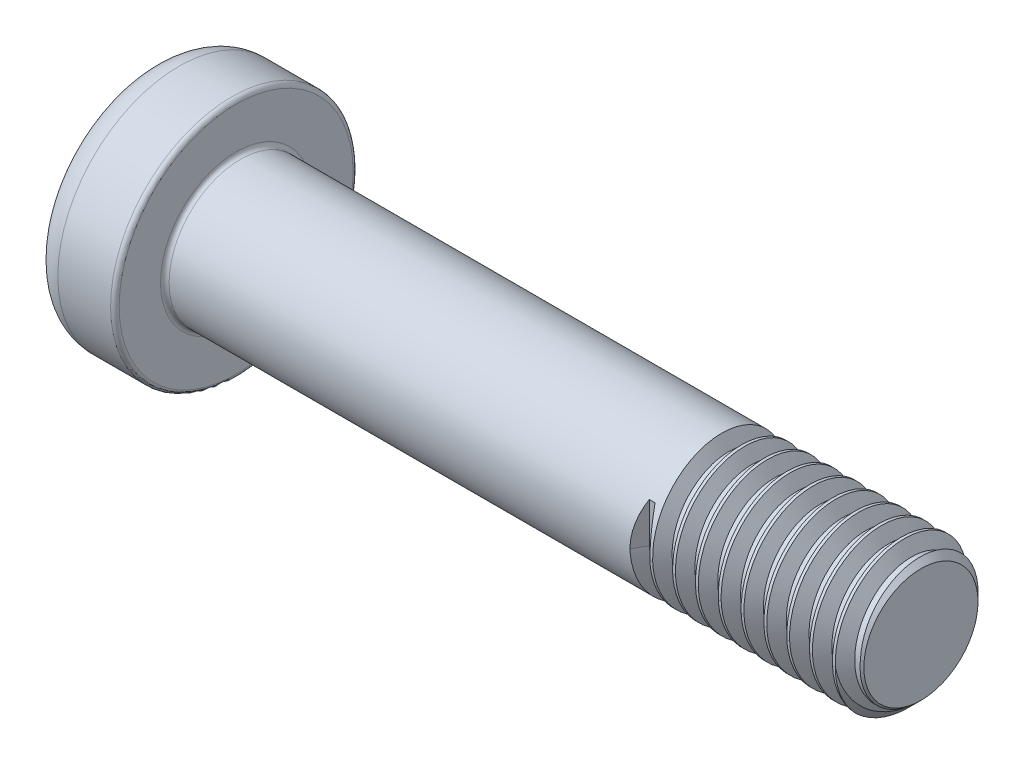
SolidWorks part; units mm, degrees
material "Acier inoxydable chromé"
ref_plane "Front Plane" through (0, 0, 0) normal (0, 0, 1) x (1, 0, 0)
ref_plane "Top Plane" through (0, 0, 0) normal (0, 1, 0) x (1, 0, 0)
ref_plane "Right Plane" through (0, 0, 0) normal (1, 0, 0) x (0, 0, -1)
sketch "Esquisse1" plane through (0, 0, 0) normal (0, 0, 1) x (1, 0, 0)
  line L0 (-10.0862, 0) -> (41.9828, 0) construction
  line L1 (0, 0) -> (0, 3.25)
  line L2 (1, 4.25) -> (3, 4.25)
  line L3 (3, 4.25) -> (3, 2.5)
  line L4 (3, 2.5) -> (27, 2.5)
  line L5 (27, 2.5) -> (27, 0)
  line L6 (27, 0) -> (0, 0)
  arc A0 (1, 4.25) -> (0, 3.25) centre (1, 3.25) ccw
  point P11 (0, 4.25)
  dimension "D5" = 1
  dimension "D1" = 5
  dimension "D4" = 8.5
revolve "Révolution1" add sketch "Esquisse1" angle 360 about L0
chamfer "Chanfrein1" distance 0.5 angle 45 1 edges at (27, 0, 2.5)
sketch "Esquisse2" plane through (0, 0, 0) normal (-1, 0, 0) x (0, 0, 1)
  line L1 (-2, 1.1547) -> (-2, -1.1547)
  line L2 (-2, -1.1547) -> (0, -2.3094)
  line L3 (0, -2.3094) -> (2, -1.1547)
  line L4 (2, -1.1547) -> (2, 1.1547)
  line L5 (2, 1.1547) -> (0, 2.3094)
  line L6 (0, 2.3094) -> (-2, 1.1547)
  circle A0 centre (0, 0) radius 2 construction
  dimension "D1" = 4
extrude "Enlèv. mat.-Extru.1" cut sketch "Esquisse2" against normal blind 3.5
sketch "Esquisse3" plane through (0, 0, 0) normal (0, 0, 1) x (1, 0, 0)
  line L0 (3.5, 0) -> (3.5, 2.3)
  line L1 (3.5, 1.1547) -> (3.5, -1.1547) construction
  line L2 (3.5, 2.3094) -> (3.5, 1.1547) construction
  line L3 (3.5, 2.3) -> (4, 0)
  line L4 (4, 0) -> (3.5, 0)
  line L5 (-3.9508, 0) -> (9.9229, 0) construction
  dimension "D1" = 2.3
  dimension "D2" = 0.5
revolve "Enlèvement de matière-Révolution1" cut sketch "Esquisse3" angle 360 about L5
fillet "Congé2" radius 0.15 8 edges at (0, -1.7321, -1) (0, -1.7321, 1) (0, 0, 2) (0, 1.7321, 1) (0, 1.7321, -1) (0, 0, -2) (3, 0, 2.5) (3, 0, 4.25)
thread "Filetage1" pitch 0.8 method cut profile "Profil de filetage1" start angle 0, offset 1, length 8, pitch 0.8, diameter 5
ref_plane "Plan1" through (28, 0, 2.5) normal (0, -1, 0) x (0, 0, 1)
sketch "Profil de filetage1" plane through (28, 0, 2.5) normal (0, -1, 0) x (0, 0, 1)
  line L0 (0, 0) -> (0, 0.8) construction
  line L11 (0, 0) -> (0, 0.7)
  line L12 (0, 0.7) -> (-0.433, 0.45)
  line L13 (-0.433, 0.45) -> (-0.433, 0.25)
  line L15 (-0.433, 0.25) -> (0, 0)
  line L17 (-0.433, 0.35) -> (0, 0.35) construction
  point P2 (0, 0)
  dimension "Pitch" = 0.8
  dimension "Profile_Angle" = 60
  dimension "Profile_Land" = 0.2
  dimension "Profile_Height" = 0.433
sketch "Esquisse6" plane through (0, 0, 0) normal (0, -1, 0) x (1, 0, 0)
  line L4 (19.75, 2.067) -> (20, 2.5)
  line L5 (20, 2.5) -> (19.3, 2.5)
  line L6 (19.3, 2.5) -> (19.55, 2.067)
  line L7 (19.55, 2.067) -> (19.75, 2.067)
  line L8 (19.75, 2.067) -> (20, 2.5)
  line L10 (19.3, 2.5) -> (19.55, 2.067)
  line L11 (19.55, 2.067) -> (19.75, 2.067)
  line L18 (20, 2.5) -> (19.3, 2.5)
  dimension "D1" = 0
extrude "Enlèv. mat.-Extru.2" cut sketch "Esquisse6" against normal blind 3.5
equation "\"Diametre\"= 5mm"
equation "\"Longueur\"= 35mm"
equation "\"D1@Esquisse1\"=\"Diametre\""
equation "\"HauteurTete\"= 5mm"
equation "\"Empreinte\"= 4mm"
equation "\"Chanfrein\"= 0.5mm"
equation "\"CongéSec\"= 0.15mm"
equation "\"DiametreTete\"= 8.5mm"
equation "\"D4@Esquisse1\"=\"DiametreTete\""
equation "\"D1@Chanfrein1\"=\"Chanfrein\""
equation "\"D1@Esquisse2\"=\"Empreinte\""
equation "\"D1@Congé2\"=\"CongéSec\""
equation "\"LongueurFil\"= 26mm"
equation "\"D4@Filetage1\" = \"LongueurFil\""
